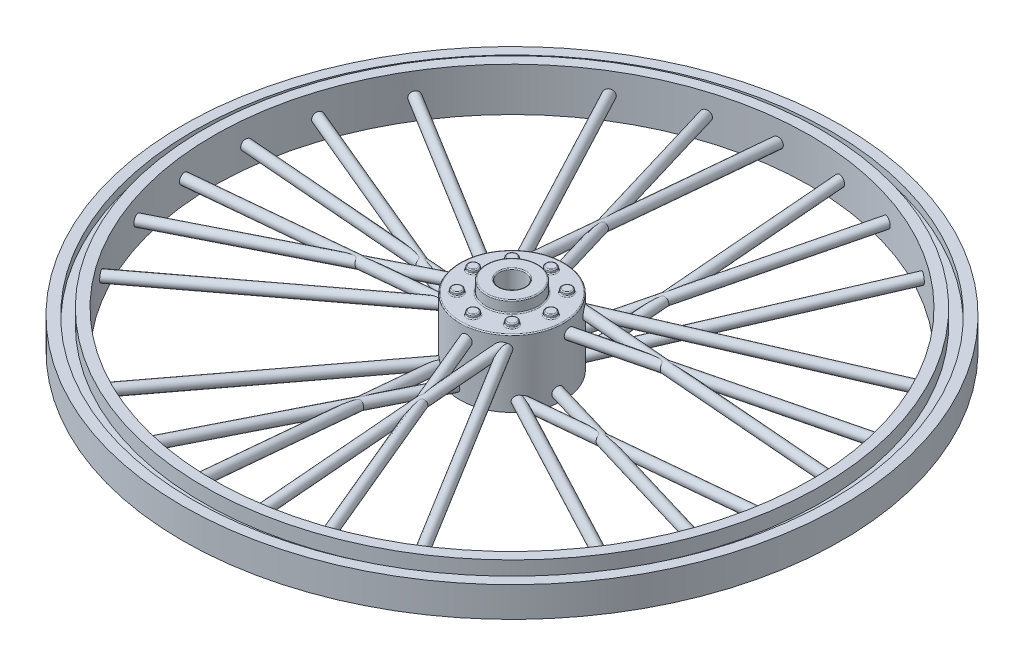
SolidWorks part; units mm, degrees
material "6061-T6 (SS)"
ref_plane "Front Plane" through (0, 0, 0) normal (0, 0, 1) x (1, 0, 0)
ref_plane "Top Plane" through (0, 0, 0) normal (0, 1, 0) x (1, 0, 0)
ref_plane "Right Plane" through (0, 0, 0) normal (1, 0, 0) x (0, 0, -1)
sketch "Sketch1" plane through (0, 0, 0) normal (1, 0, 0) x (0, 0, -1)
  line L0 (0, 0) -> (31.75, 0) construction
  line L1 (0, 0) -> (0, 21.0135) construction
  line L2 (30.75, 1.45) -> (31.75, 1.45)
  line L3 (30.75, 1.45) -> (30.75, 0.7)
  line L4 (30.75, -1.45) -> (31.75, -1.45)
  line L5 (31.75, 1.45) -> (31.75, -1.45)
  line L6 (30.75, -0.7) -> (30.75, -1.45)
  line L7 (29.75, 0.7) -> (30.75, 0.7)
  line L9 (29.75, -0.7) -> (30.75, -0.7)
  line L14 (28.75, 2.1) -> (29.75, 2.1)
  line L15 (28.75, 2.1) -> (28.75, -2.1)
  line L16 (28.75, -2.1) -> (29.75, -2.1)
  line L18 (29.75, 2.1) -> (29.75, 0.7)
  line L19 (29.75, -0.7) -> (29.75, -2.1)
  line L20 (30.25, 0.7) -> (30.25, -0.7) construction
  point P14 (30.25, 0)
  point P16 (31.75, 0)
  dimension "D1" = 63.5
  dimension "D3" = 2.9
  dimension "D4" = 4.2
  dimension "D5" = 1.4
  dimension "D6" = 1
revolve "Revolve2" add sketch "Sketch1" angle 360 about L1
sketch "Sketch2" plane through (0, 0, 0) normal (0, 1, 0) x (1, 0, 0)
  circle A0 centre (0, 0) radius 5
  dimension "D1" = 10
extrude "Boss-Extrude1" add sketch "Sketch2" along normal blind 6.5 from offset 3.1 separate body offset against normal yes
ref_axis "Axis1" through (0, 6.7291, 0) along (0, -1, 0)
ref_plane "Plane1" through (0, 0, 0) normal (0.866, 0, 0.5) x (0.5, 0, -0.866)
ref_plane "STRAIGHT" through (3, 0, 0) normal (1, 0, 0) x (0, 0, -1)
ref_axis "Axis2" through (3, -54.3, 0) along (0, 1, 0)
sketch "Sketch3" plane through (3, 0, 0) normal (1, 0, 0) x (0, 0, -1)
  line L0 (-29.5984, 0) -> (0, 2.5895)
  line L1 (-29.5984, 0) -> (-12.1475, 0) construction
  line L2 (0, 0) -> (0, 2.5895) construction
  line L5 (-29.5984, 0) -> (-29.5984, 2.1) construction
  line L6 (28.75, 2.1) -> (-28.75, 2.1) construction
  dimension "D1" = 5
  dimension "29.5" = 29.5984
sweep "Sweep1" add path "Sketch3" circular profile diameter 1 parameters "D3"=1
ref_plane "ref x1" through (2.6491, 0, -0.9642) normal (-0.9397, 0, 0.342) x (0.342, 0, 0.9397)
ref_plane "offset ref x1" through (-1.1097, 0, 0.4039) normal (-0.9397, 0, 0.342) x (0.342, 0, 0.9397)
sketch "Sketch4" plane through (-1.1097, 0, 0.4039) normal (-0.9397, 0, 0.342) x (0.342, 0, 0.9397)
  line L0 (29.7266, 0) -> (0, 2.6007)
  line L1 (29.7266, 0) -> (16.1941, 0) construction
  line L2 (29.7266, 0) -> (29.7266, 2.1) construction
  line L3 (0, 0) -> (0, 2.6007) construction
  line L4 (28.75, 2.1) -> (-28.75, 2.1) construction
  dimension "D1" = 5
sweep "Sweep2" add path "Sketch4" circular profile diameter 1 parameters "D3"=1
ref_plane "ref y1" through (2.25, 0, -1.299) normal (0.866, 0, -0.5) x (-0.5, 0, -0.866)
ref_plane "offset ref y1" through (0.7345, 0, -0.424) normal (0.866, 0, -0.5) x (-0.5, 0, -0.866)
sketch "Sketch5" plane through (0.7345, 0, -0.424) normal (0.866, 0, -0.5) x (-0.5, 0, -0.866)
  line L0 (-29.7379, 0) -> (-29.7379, 2.1) construction
  line L1 (0, 2.6017) -> (0, 0) construction
  line L2 (-29.7379, 0) -> (-18.3884, 0) construction
  line L7 (-29.7379, 0) -> (0, 2.6017)
  dimension "D1" = 5
sweep "Sweep3" add path "Sketch5" circular profile diameter 1 parameters "D3"=1
sketch "Sketch6" plane through (3, 0, 0) normal (1, 0, 0) x (0, 0, -1)
  line L0 (0, -2.5895) -> (29.5984, 0)
  line L1 (29.5984, 0) -> (0, 0) construction
  line L2 (0, -2.5895) -> (0, 0) construction
  line L3 (29.5984, 0) -> (29.5984, 2.1) construction
  line L4 (28.75, 2.1) -> (-28.75, 2.1) construction
  dimension "D1" = 5
sweep "Sweep4" add path "Sketch6" circular profile diameter 1 parameters "D3"=1
ref_plane "ref x2" through (2.6491, 0, 0.9642) normal (0.9397, 0, 0.342) x (0.342, 0, -0.9397)
ref_plane "offset ref x2" through (-1.1097, 0, -0.4039) normal (0.9397, 0, 0.342) x (0.342, 0, -0.9397)
sketch "Sketch7" plane through (-1.1097, 0, -0.4039) normal (0.9397, 0, 0.342) x (0.342, 0, -0.9397)
  line L0 (29.7266, 0) -> (0, -2.6007)
  line L1 (0, -2.6007) -> (0, 0) construction
  line L3 (19.3488, 0) -> (29.7266, 0) construction
  line L4 (29.7266, 0) -> (29.7266, 2.1) construction
  dimension "D1" = 5
sweep "Sweep5" add path "Sketch7" circular profile diameter 1 parameters "D3"=1
ref_plane "ref y2" through (2.25, 0, 1.299) normal (-0.866, 0, -0.5) x (-0.5, 0, 0.866)
ref_plane "offset ref y2" through (0.7345, 0, 0.424) normal (-0.866, 0, -0.5) x (-0.5, 0, 0.866)
sketch "Sketch8" plane through (0.7345, 0, 0.424) normal (-0.866, 0, -0.5) x (-0.5, 0, 0.866)
  line L0 (-29.7379, 0) -> (0, -2.6017)
  line L1 (0, -2.6017) -> (0, 0) construction
  line L2 (-17.5286, 0) -> (-29.7379, 0) construction
  line L3 (-29.7379, 0) -> (-29.7379, 2.1) construction
  dimension "D1" = 5
sweep "Sweep6" add path "Sketch8" circular profile diameter 1 parameters "D3"=1
pattern_circular "CirPattern1" count 4 over 360 about axis through (0, 3.4, 0) along (0, 1, 0) of "Sweep2", "Sweep3", "Sweep1", "Sweep4", "Sweep5", "Sweep6"
sketch "Sketch9" plane through (0, -3.1, 0) normal (0, -1, 0) x (1, 0, 0)
  circle A1 centre (0, 0) radius 4
  dimension "D1" = 8
extrude "Cut-Extrude1" cut sketch "Sketch9" against normal blind 5
sketch "Sketch10" plane through (0, 1.9, 0) normal (0, -1, 0) x (1, 0, 0)
  line L1 (-2, 1.1547) -> (-2, -1.1547)
  line L2 (-2, -1.1547) -> (0, -2.3094)
  line L3 (0, -2.3094) -> (2, -1.1547)
  line L4 (2, -1.1547) -> (2, 1.1547)
  line L5 (2, 1.1547) -> (0, 2.3094)
  line L6 (0, 2.3094) -> (-2, 1.1547)
  circle A0 centre (0, 0) radius 2 construction
  dimension "D1" = 4
extrude "Boss-Extrude2" add sketch "Sketch10" along normal up to surface (5 mm away) up to face at (0, -3.1, -4)
sketch "Sketch11" plane through (0, 3.4, 0) normal (0, 1, 0) x (1, 0, 0)
  circle A0 centre (0, 0) radius 2.5
  dimension "D1" = 5
extrude "Boss-Extrude3" add sketch "Sketch11" along normal blind 1.1
sketch "Sketch12" plane through (0, 4.5, 0) normal (0, 1, 0) x (1, 0, 0)
  circle A0 centre (0, 0) radius 1.25
  dimension "D1" = 2.5
extrude "Cut-Extrude2" cut sketch "Sketch12" against normal through all
sketch "Sketch13" plane through (0, 3.4, 0) normal (0, 1, 0) x (1, 0, 0)
  line L0 (-5, 0) -> (-2.5, 0) construction
  circle A0 centre (-3.75, 0) radius 0.5
  circle A1 centre (0, 0) radius 5 construction
  circle A2 centre (0, 0) radius 2.5 construction
  point P3 (-3.75, 0)
  dimension "D1" = 1
extrude "Boss-Extrude4" add sketch "Sketch13" along normal blind 0.35
fillet "Fillet2" radius 0.1 11 edges at (0, 4.5, 2.5) (0, 3.4, 2.5) (-1, -3.1, 1.7321) (1, -3.1, 1.7321) (2, -3.1, 0) (1, -3.1, -1.7321) (-1, -3.1, -1.7321) (-2, -3.1, 0) (0, -3.1, 1.25) (0, 4.5, 1.25) (0, 3.4, 5)
fillet "Fillet3" radius 0.1 2 edges at (-3.75, 3.4, 0.5) (-3.75, 3.75, 0.5)
pattern_circular "CirPattern3" count 8 over 360 about axis through (0, 3.3, 0) along (0, -1, 0) of "Boss-Extrude4", "Fillet3"
fillet "Fillet4" radius 0.5 12 edges at (1.9707, -3.0707, 1.1378) (0, -3.0707, 2.2756) (-1.9707, -3.0707, 1.1378) (-1.9707, -3.0707, -1.1378) (0, -3.0707, -2.2756) (1.9707, -3.0707, -1.1378) (2, -0.55, -1.1547) (0, -0.55, -2.3094) (-2, -0.55, -1.1547) (-2, -0.55, 1.1547) (0, -0.55, 2.3094) (2, -0.55, 1.1547)
ref_axis "Axis3" through (0, -3, 0) along (0, 1, 0)
equation "\"spk\"= 5"
equation "\"D1@Sketch3\"=\"spk\""
equation "\"D1@Sketch4\"=\"spk\""
equation "\"D1@Sketch6\" = \"spk\""
equation "\"x_angle\"= 160"
equation "\"D1@ref x1\" = \"x_angle\""
equation "\"D1@ref x2\" = 180 - \"x_angle\""
equation "\"D1@Sketch7\" = \"spk\""
equation "\"D1@Sketch5\"=\"spk\""
equation "\"D1@ref y1\"= \"y_angle\""
equation "\"y_angle\"= 30"
equation "\"D1@ref y2\"= 180 - \"y_angle\""
equation "\"D1@Sketch8\" = \"spk\""
